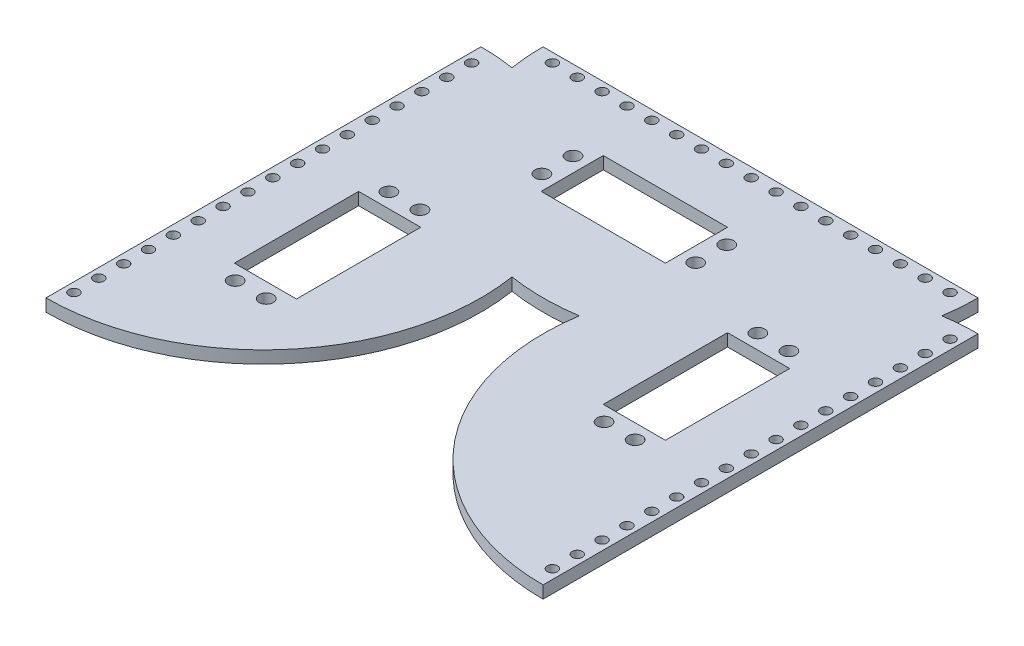
SolidWorks part; units mm, degrees
ref_plane "前视基准面" through (0, 0, 0) normal (0, 0, 1) x (1, 0, 0)
ref_plane "上视基准面" through (0, 0, 0) normal (0, 1, 0) x (1, 0, 0)
ref_plane "右视基准面" through (0, 0, 0) normal (1, 0, 0) x (0, 0, -1)
sketch "草图1" plane through (0, 0, 0) normal (0, 1, 0) x (1, 0, 0)
  line L0 (-50, 0) -> (50, 0)
  arc A0 (50, 0) -> (-50, 0) centre (0, 0) cw
extrude "凸台-拉伸1" add sketch "草图1" along normal blind 4
sketch "草图2" plane through (0, 4, 0) normal (0, 1, 0) x (1, 0, 0)
  line L2 (0, -10.623) -> (10, -10.623)
  line L3 (10, -10.623) -> (10, -30.623)
  line L4 (10, -30.623) -> (-30, -30.623)
  line L5 (-30, -30.623) -> (-30, -10.623)
  line L6 (-30, -10.623) -> (0, -10.623)
extrude "切除-拉伸1" cut sketch "草图2" against normal blind 10
sketch "草图3" plane through (0, 4, 0) normal (0, 1, 0) x (1, 0, 0)
  circle A0 centre (-34.75, -15.623) radius 2.25
  circle A1 centre (-34.75, -25.623) radius 2.25
  circle A2 centre (14.75, -25.623) radius 2.25
  circle A3 centre (14.75, -15.623) radius 2.25
extrude "切除-拉伸2" cut sketch "草图3" against normal blind 10
sketch "草图4" plane through (0, 4, 0) normal (0, 1, 0) x (1, 0, 0)
  circle A0 centre (0, -3) radius 1.65
  circle A1 centre (8, -3) radius 1.65
  circle A2 centre (16, -3) radius 1.65
  circle A3 centre (24, -3) radius 1.65
  circle A4 centre (32, -3) radius 1.65
  circle A5 centre (40, -3) radius 1.65
  circle A6 centre (-40, -3) radius 1.65
  circle A7 centre (-32, -3) radius 1.65
  circle A8 centre (-24, -3) radius 1.65
  circle A9 centre (-16, -3) radius 1.65
  circle A10 centre (-8, -3) radius 1.65
extrude "切除-拉伸3" cut sketch "草图4" against normal blind 10
sketch "草图5" plane through (0, 4, 0) normal (0, 1, 0) x (1, 0, 0)
  line L0 (-70, 0) -> (70, 0)
  circle A0 centre (0, 0) radius 70
  circle A1 centre (0, 0) radius 50
  arc M20 (-50, 0) -> (50, 0) centre (0, 0) ccw
extrude "凸台-拉伸2" add sketch "草图5" against normal blind 4 contours L0 A0 M20 region at (-60, 4, 1.5652)
sketch "草图6" plane through (0, 4, 0) normal (0, 1, 0) x (1, 0, 0)
  circle A0 centre (0, -3) radius 1.65
  circle A1 centre (8, -3) radius 1.65
  circle A2 centre (16, -3) radius 1.65
  circle A3 centre (24, -3) radius 1.65
  circle A4 centre (32, -3) radius 1.65
  circle A5 centre (40, -3) radius 1.65
  circle A6 centre (48, -3) radius 1.65
  circle A7 centre (56, -3) radius 1.65
  circle A8 centre (64, -3) radius 1.65
  circle A9 centre (-8, -3) radius 1.65
  circle A10 centre (-16, -3) radius 1.65
  circle A11 centre (-24, -3) radius 1.65
  circle A12 centre (-32, -3) radius 1.65
  circle A13 centre (-40, -3) radius 1.65
  circle A14 centre (-48, -3) radius 1.65
  circle A15 centre (-56, -3) radius 1.65
  circle A16 centre (-64, -3) radius 1.65
  dimension "D1" = 9
  dimension "D2" = 8
extrude "切除-拉伸4" cut sketch "草图6" against normal blind 4
sketch "草图7" plane through (0, 4, 0) normal (0, 1, 0) x (1, 0, 0)
  line L1 (-30, -20.623) -> (-30, -30.623)
  line L2 (10, -20.623) -> (10, -30.623)
  line L3 (-30, -30.623) -> (10, -30.623)
  line L4 (-30, -10.623) -> (-30, -30.623) construction
  line L5 (10, -30.623) -> (10, -10.623) construction
  line L7 (-30, -20.623) -> (10, -20.623)
  line L8 (-30, -20.623) -> (-30, -40.623)
  line L9 (10, -20.623) -> (10, -40.623)
  line L10 (-30, -40.623) -> (10, -40.623)
  line L11 (-34.75, -15.623) -> (14.75, -15.623)
  line L12 (14.75, -15.623) -> (14.75, -25.623)
  line L13 (14.75, -25.623) -> (14.75, -35.623)
  line L14 (-34.75, -15.623) -> (-34.75, -25.623)
  line L15 (-34.75, -25.623) -> (-34.75, -35.623)
  circle A1 centre (-34.75, -35.623) radius 2.25
  circle A2 centre (14.75, -35.623) radius 2.25
  line M30 (10, -30.623) -> (-30, -30.623)
extrude "切除-拉伸5" cut sketch "草图7" against normal blind 4 contours A1 | L8 L10 L9 M30 | A2 region at (-10, 4, 35.623) region at (16.296, 4, 34.0771) region at (-33.204, 4, 34.0771)
sketch "草图8" plane through (0, 4, 0) normal (0, 1, 0) x (1, 0, 0)
  line L0 (-34.75, -15.623) -> (14.75, -15.623)
  line L1 (14.75, -15.623) -> (14.75, -25.623)
  line L2 (14.75, -25.623) -> (14.75, -20.623)
  line L3 (14.75, -20.623) -> (-41.5549, -20.623)
  line L4 (-41.5549, -20.623) -> (-41.5549, -8.5064)
  line L5 (-41.5549, -8.5064) -> (21.0409, -8.9873)
  line L6 (21.0409, -8.9873) -> (21.0409, -20.623)
  line L7 (21.0409, -20.623) -> (14.75, -20.623)
  line M3 (-30, -40.623) -> (-30, -10.623)
  line M4 (-30, -10.623) -> (10, -10.623)
  line M5 (10, -10.623) -> (10, -40.623)
  circle M24 centre (14.75, -15.623) radius 2.25
  circle M27 centre (-34.75, -15.623) radius 2.25
extrude "凸台-拉伸4" add sketch "草图8" against normal blind 4 contours M27 | L3 L0 M5 M3 | L1 L0 M24 | L0 L1 M24 | L0 M3 M5 M4 region at (-10, 4, 13.123) region at (-10, 4, 18.123) region at (-36.9364, 4, 15.623) region at (15.0683, 4, 15.3047) region at (13.7951, 4, 16.578)
sketch "草图9" plane through (0, 4, 0) normal (0, 1, 0) x (1, 0, 0)
  line L0 (0, -70) -> (0, -80)
  line L1 (0, -80) -> (-10, -80)
  line L2 (-10, -80) -> (10, -80)
  line L3 (80, -80) -> (77, -80)
  line L4 (80, -10) -> (80, -150)
  line L5 (-30, -20.623) -> (10, -20.623)
  line L6 (-30, -20.623) -> (-30, -40.623)
  line L7 (10, -20.623) -> (10, -40.623)
  line L8 (-30, -40.623) -> (10, -40.623)
  line L9 (59.377, -90) -> (39.377, -90)
  line L10 (59.377, -50) -> (59.377, -90)
  line L11 (59.377, -50) -> (39.377, -50)
  line L12 (39.377, -50) -> (39.377, -90)
  line L17 (-59.377, -70) -> (-39.377, -70)
  line L18 (-59.377, -110) -> (-59.377, -70)
  line L19 (-59.377, -110) -> (-39.377, -110)
  line L20 (-39.377, -110) -> (-39.377, -70)
  line L21 (-80, -10) -> (-80, -150)
  arc A1 (80, -10) -> (80, -150) centre (80, -80) ccw
  circle A2 centre (77, -80) radius 1.65
  circle A3 centre (77, -72) radius 1.65
  circle A4 centre (77, -64) radius 1.65
  circle A5 centre (77, -56) radius 1.65
  circle A6 centre (77, -48) radius 1.65
  circle A7 centre (77, -40) radius 1.65
  circle A8 centre (77, -32) radius 1.65
  circle A9 centre (77, -24) radius 1.65
  circle A10 centre (77, -16) radius 1.65
  circle A11 centre (77, -88) radius 1.65
  circle A12 centre (77, -96) radius 1.65
  circle A13 centre (77, -104) radius 1.65
  circle A14 centre (77, -112) radius 1.65
  circle A15 centre (77, -120) radius 1.65
  circle A16 centre (77, -128) radius 1.65
  circle A17 centre (77, -136) radius 1.65
  circle A18 centre (77, -144) radius 1.65
  circle A19 centre (14.75, -25.623) radius 2.25
  circle A20 centre (14.75, -35.623) radius 2.25
  circle A21 centre (-34.75, -25.623) radius 2.25
  circle A22 centre (-34.75, -35.623) radius 2.25
  circle A23 centre (44.377, -45.25) radius 2.25
  circle A24 centre (54.377, -45.25) radius 2.25
  circle A25 centre (54.377, -94.75) radius 2.25
  circle A26 centre (44.377, -94.75) radius 2.25
  circle A31 centre (-44.377, -114.75) radius 2.25
  circle A32 centre (-54.377, -114.75) radius 2.25
  circle A33 centre (-54.377, -65.25) radius 2.25
  circle A34 centre (-44.377, -65.25) radius 2.25
  circle A35 centre (-77, -144) radius 1.65
  circle A36 centre (-77, -136) radius 1.65
  circle A37 centre (-77, -128) radius 1.65
  circle A38 centre (-77, -120) radius 1.65
  circle A39 centre (-77, -112) radius 1.65
  circle A40 centre (-77, -104) radius 1.65
  circle A41 centre (-77, -96) radius 1.65
  circle A42 centre (-77, -88) radius 1.65
  circle A43 centre (-77, -80) radius 1.65
  circle A44 centre (-77, -72) radius 1.65
  circle A45 centre (-77, -64) radius 1.65
  circle A46 centre (-77, -56) radius 1.65
  circle A47 centre (-77, -48) radius 1.65
  circle A48 centre (-77, -40) radius 1.65
  circle A49 centre (-77, -32) radius 1.65
  circle A50 centre (-77, -24) radius 1.65
  circle A51 centre (-77, -16) radius 1.65
  arc A52 (-80, -10) -> (-80, -150) centre (-80, -80) cw
  point P61 (0, 0)
  point P62 (0, 0)
  point P63 (0, 0)
  point P100 (0, -80)
extrude "凸台-拉伸7" add sketch "草图9" against normal blind 4 contours A24 L9 L11 L10 L12 A1 L4 A2 A26 A25 A18 A17 A16 A15 A14 A13 A12 A11 A10 A9 A8 A7 A6 A5 A4 | A52 L21 L9 A50 A48 A46 A44 A42 A40 A38 A36 L20 L19 L18 L17 A31 A32 A33 A34 A35 A37 A39 A41 A43 A45 A47 A49 region at (-31.6093, 4, 128.3907) region at (31.6093, 4, 31.6093)
sketch "草图10" plane through (0, 4, 0) normal (0, 1, 0) x (1, 0, 0)
  line L0 (59.377, -50) -> (59.377, -90)
  line L1 (59.377, -50) -> (39.377, -50)
  line L2 (59.377, -90) -> (39.377, -90)
  line L3 (39.377, -50) -> (39.377, -90)
  circle A0 centre (54.377, -45.25) radius 2.25
  circle A1 centre (44.377, -45.25) radius 2.25
extrude "切除-拉伸6" cut sketch "草图10" against normal blind 4
